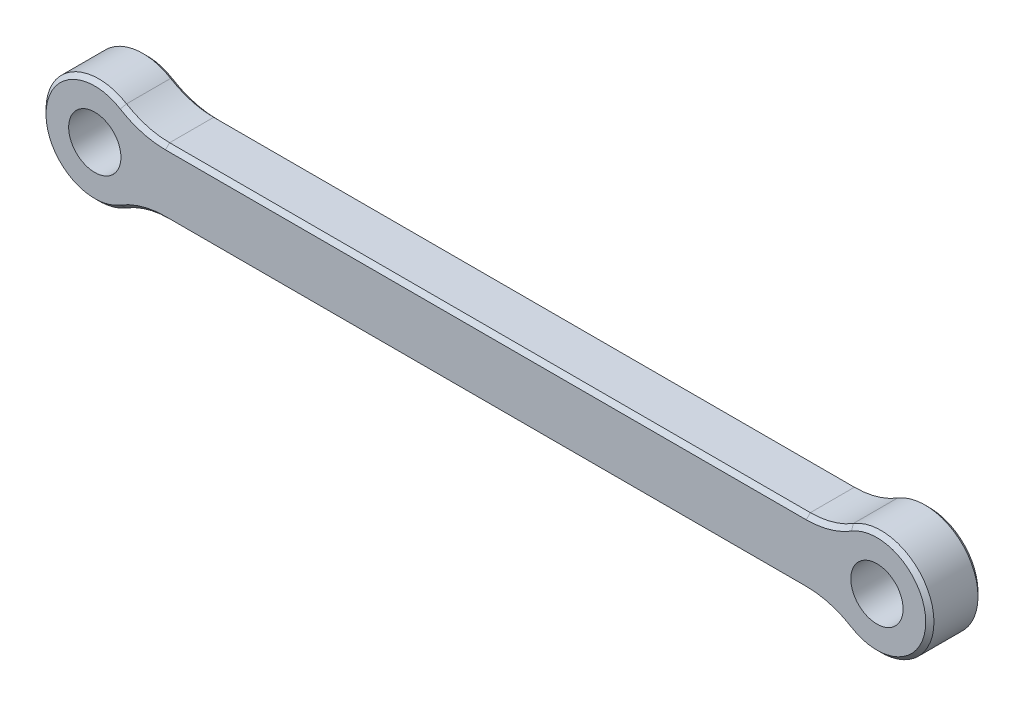
SolidWorks part; units mm, degrees
ref_plane "Front Plane" through (0, 0, 0) normal (0, 0, 1) x (1, 0, 0)
ref_plane "Top Plane" through (0, 0, 0) normal (0, 1, 0) x (1, 0, 0)
ref_plane "Right Plane" through (0, 0, 0) normal (1, 0, 0) x (0, 0, -1)
sketch "Sketch2" plane through (0, 0, 0) normal (0, 0, 1) x (1, 0, 0)
  line L0 (0, 0) -> (95, 0) construction
  line L5 (0, 0) -> (95, 0) construction
  line L6 (0, 4) -> (95, 4)
  line L7 (0, -4) -> (95, -4)
  circle A0 centre (0, 0) radius 6.425
  circle A5 centre (0, 0) radius 3.175
  circle A6 centre (95, 0) radius 3.175
  arc A7 (0, 4) -> (0, -4) centre (0, 0) ccw
  arc A8 (95, -4) -> (95, 4) centre (95, 0) ccw
  circle A9 centre (95, 0) radius 6.425
  point P17 (47.5, 0)
  dimension "D5" = 6.35
  dimension "D2" = 12.85
  dimension "D1" = 95
  dimension "D7" = 8
  dimension "D8" = 95
extrude "Boss-Extrude1" add sketch "Sketch2" along normal blind 6.35 contours A9 L6 A0 L7 | L6 A9 L7 A8 A6 | L7 A9 L6 A8 | L6 A7 L7 A0 A5 | A7 L6 A0 L7 | A9 | A6 region at (-4.1721, 0, 0) region at (2.514, 3.8686, 0) region at (47.5, 0, 0) region at (97.0617, 5.9032, 0) region at (92.486, 3.8686, 0)
fillet "Fillet1" radius 10 4 edges at (89.972, 4, 3.175) (89.972, -4, 3.175) (5.028, -4, 3.175) (5.028, 4, 3.175)
chamfer "Chamfer1" distance 0.5 angle 45 16 edges at (47.5, -4, 0) (47.5, 4, 0) (47.5, -4, 6.35) (47.5, 4, 6.35) (5.8726, -4.3762, 0) (89.1274, -4.3762, 0) (-6.425, 0, 0) (101.425, 0, 0) (5.8726, 4.3762, 0) (89.1274, 4.3762, 0) (5.8726, -4.3762, 6.35) (89.1274, -4.3762, 6.35) (-6.425, 0, 6.35) (101.425, 0, 6.35) (5.8726, 4.3762, 6.35) (89.1274, 4.3762, 6.35)
ref_point "Point1"
equation "\"D2@Sketch2\"=\"D5@Sketch2\"+6.5mm"
